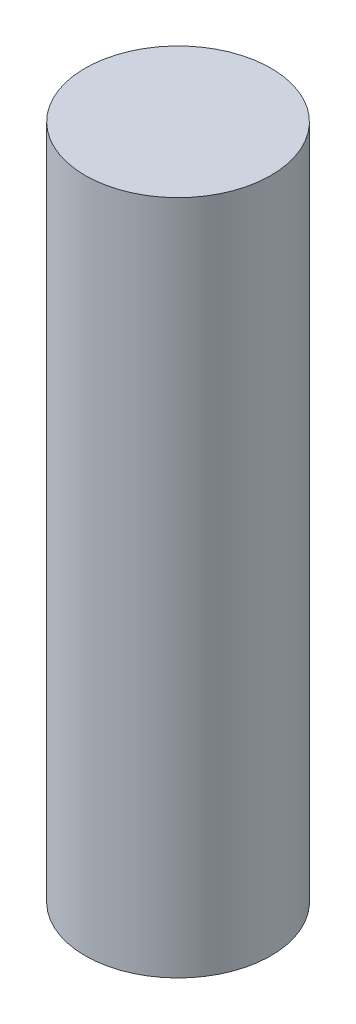
SolidWorks part; units mm, degrees
material "Сталь 3 ГОСТ 535-88"
ref_plane "Спереди" through (0, 0, 0) normal (0, 0, 1) x (1, 0, 0)
ref_plane "Сверху" through (0, 0, 0) normal (0, 1, 0) x (1, 0, 0)
ref_plane "Справа" through (0, 0, 0) normal (1, 0, 0) x (0, 0, -1)
sketch "Эскиз1" plane through (0, 0, 0) normal (0, 1, 0) x (1, 0, 0)
  circle A0 centre (0, 0) radius 2.75
  dimension "D1" = 5.5
extrude "Бобышка-Вытянуть1" add sketch "Эскиз1" along normal blind 10 and the other way blind 10
sketch "Эскиз2" plane through (0, 0, 0) normal (1, 0, 0) x (0, 0, -1)
  line L0 (0, -19.6379) -> (0, 19.6379) construction
  point P3 (0, 0)
